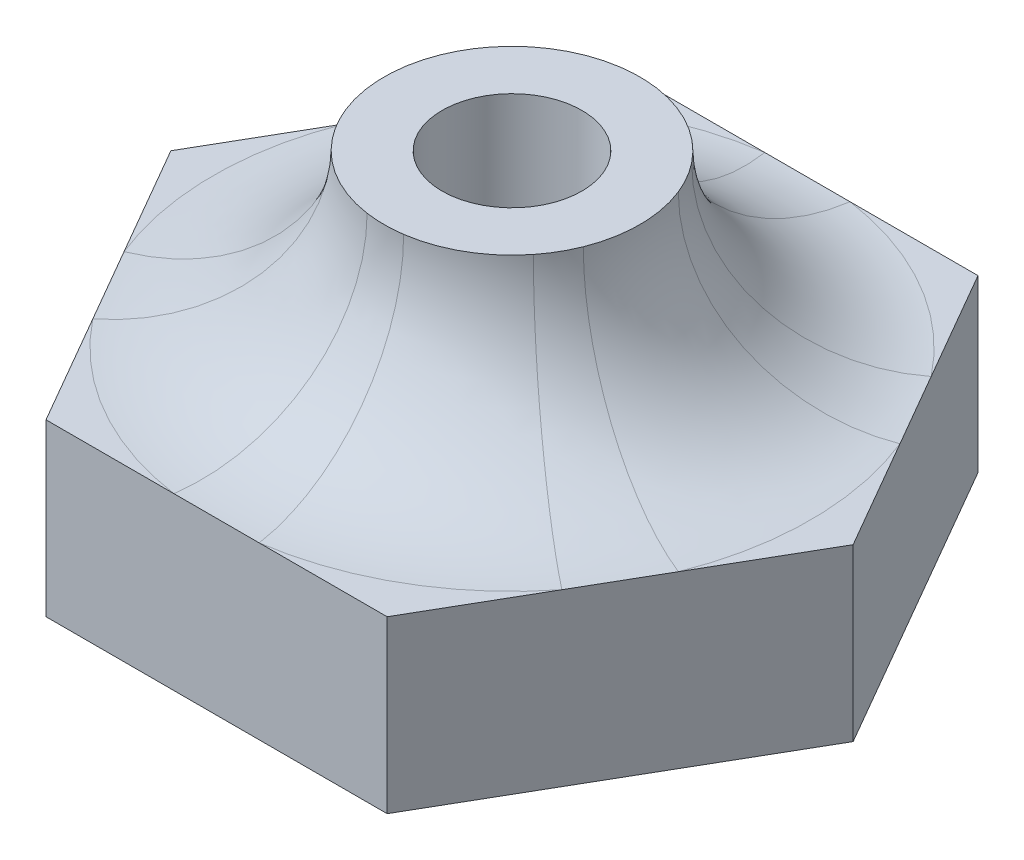
SolidWorks part; units mm, degrees
ref_plane "Спереди" through (0, 0, 0) normal (0, 0, 1) x (1, 0, 0)
ref_plane "Сверху" through (0, 0, 0) normal (0, 1, 0) x (1, 0, 0)
ref_plane "Справа" through (0, 0, 0) normal (1, 0, 0) x (0, 0, -1)
sketch "Sketch1" plane through (0, 0, 0) normal (0, 1, 0) x (1, 0, 0)
  line L1 (-10, 17.3205) -> (-20, 0)
  line L2 (-20, 0) -> (-10, -17.3205)
  line L3 (-10, -17.3205) -> (10, -17.3205)
  line L4 (10, -17.3205) -> (20, 0)
  line L5 (20, 0) -> (10, 17.3205)
  line L6 (10, 17.3205) -> (-10, 17.3205)
  circle A0 centre (0, 0) radius 20 construction
  dimension "D1" = 40
extrude "Boss-Extrude1" add sketch "Sketch1" along normal blind 10
sketch "Sketch2" plane through (0, 10, 0) normal (0, 1, 0) x (1, 0, 0)
  circle A0 centre (0, 0) radius 4.1
  dimension "D1" = 8.2
extrude "Cut-Extrude1" cut sketch "Sketch2" against normal through all
sketch "Sketch3" plane through (0, 0, 0) normal (0, -1, 0) x (1, 0, 0)
  line L0 (10, 17.3205) -> (20, 0) construction
  line L1 (7.5, 0) -> (3.75, 6.4952)
  line L2 (3.75, 6.4952) -> (-3.75, 6.4952)
  line L3 (-3.75, 6.4952) -> (-7.5, 0)
  line L4 (-7.5, 0) -> (-3.75, -6.4952)
  line L5 (-3.75, -6.4952) -> (3.75, -6.4952)
  line L6 (3.75, -6.4952) -> (7.5, 0)
  circle A0 centre (0, 0) radius 7.5 construction
  dimension "D1" = 15
extrude "Cut-Extrude2" cut sketch "Sketch3" against normal blind 8
sketch "Sketch4" plane through (0, 10, 0) normal (0, 1, 0) x (1, 0, 0)
  circle A0 centre (0, 0) radius 7.5
  circle A1 centre (0, 0) radius 4.1
  circle A2 centre (0, 0) radius 4.1 construction
  dimension "D1" = 15
extrude "Boss-Extrude2" add sketch "Sketch4" along normal blind 10
fillet "Fillet1" radius 10 1 edges at (0, 10, 7.5)
